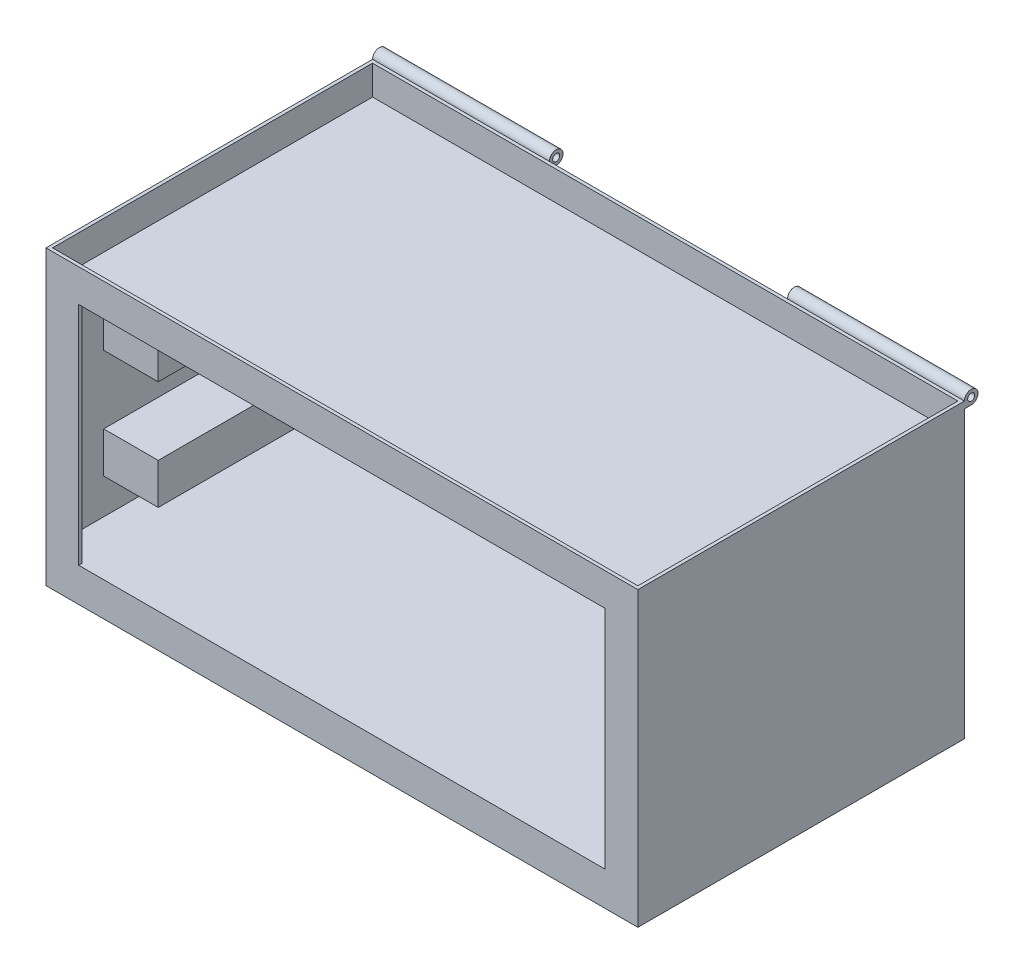
SolidWorks part; units mm, degrees
ref_plane "Front Plane" through (0, 0, 0) normal (0, 0, 1) x (1, 0, 0)
ref_plane "Top Plane" through (0, 0, 0) normal (0, 1, 0) x (1, 0, 0)
ref_plane "Right Plane" through (0, 0, 0) normal (1, 0, 0) x (0, 0, -1)
sketch "Sketch1" plane through (0, 0, 0) normal (0, 1, 0) x (1, 0, 0)
  line L0 (0, 0) -> (-1.524, 0) construction
  line L9 (0, 0) -> (273.177, 0)
  line L10 (0, 0) -> (0, 149.352)
  line L11 (0, 149.352) -> (273.177, 149.352)
  line L12 (273.177, 0) -> (273.177, 149.352)
  line L13 (-1.524, -1.524) -> (274.701, -1.524)
  line L14 (-1.524, -1.524) -> (-1.524, 150.876)
  line L15 (-1.524, 150.876) -> (274.701, 150.876)
  line L16 (274.701, -1.524) -> (274.701, 150.876)
  line L17 (0, 149.352) -> (0, 150.876) construction
  line L18 (273.177, 149.352) -> (274.701, 149.352) construction
  line L19 (273.177, 0) -> (273.177, -1.524) construction
  line L20 (13.716, 0) -> (13.716, -1.524)
  line L21 (136.5885, 150.876) -> (136.5885, -1.524) construction
  line L22 (259.461, 0) -> (259.461, -1.524)
  point P19 (0, 0)
  dimension "D1" = 1.524
  dimension "D2" = 276.225
  dimension "D3" = 152.4
  dimension "D4" = 15.24
extrude "Bulk-Extrude" add sketch "Sketch1" against normal blind 136.525 contours L14 L13 L16 L15
extrude "Inner Shell-Cut" cut sketch "Sketch1<13>" against normal offset from surface (120.65 mm away) 15.875 contours L9 L12 L11 L10 | L22 L9 L20 L13 region at (136.5885, 0, -74.676) region at (136.5885, 0, 0.762) up to face at (136.5885, -136.525, -74.676)
sketch "Sketch1<13>" plane through (0, 0, 0) normal (0, 1, 0) x (1, 0, 0) same geometry as "Sketch1"
extrude "Top Wall-Extrude" add sketch "Sketch1<14>" against normal blind 15.24 contours L22 L9 L20 L13 region at (136.5885, 0, 0.762)
sketch "Sketch1<14>" plane through (0, 0, 0) normal (0, 1, 0) x (1, 0, 0) same geometry as "Sketch1"
extrude "Top Floor-Extrude" add sketch "Sketch1<15>" along normal blind 1.524 from surface contours L9 L12 L11 L10 region at (136.5885, 0, -74.676) starting at face at (136.5885, -15.24, 0.762)
sketch "Sketch1<15>" plane through (0, 0, 0) normal (0, 1, 0) x (1, 0, 0) same geometry as "Sketch1"
ref_plane "Mid Plane" through (136.5885, 0, 0) normal (1, 0, 0) x (0, 0, -1)
sketch "Sketch5" plane through (274.701, 0, 0) normal (1, 0, 0) x (0, 0, -1)
  line L0 (150.876, 0) -> (154.051, 0)
  line L2 (154.051, -3.175) -> (150.876, -3.175)
  line L3 (150.876, -136.525) -> (150.876, 0) construction
  circle A0 centre (154.051, 0) radius 3.175
  circle A1 centre (154.051, 0) radius 1.651
  line M6 (150.876, -136.525) -> (150.876, 0)
  dimension "D1" = 1.524
  dimension "D2" = 6.35
extrude "Hinge-Extrude" add sketch "Sketch5" against normal blind 82.55 contours A1 A0 | A0 L2 M6 region at (274.701, 3.0852, -154.051) region at (274.701, -2.4658, -151.5852)
mirror "Mirror1" about plane through (136.5885, 0, 0) normal (1, 0, 0) of "Hinge-Extrude"
sketch "Sketch7" plane through (0, 0, -149.352) normal (0, 0, 1) x (1, 0, 0)
  line L0 (273.177, -120.65) -> (273.177, -15.24) construction
  line L1 (0, -34.29) -> (25.4635, -34.29)
  line L2 (0, -34.29) -> (0, -53.34)
  line L3 (0, -53.34) -> (25.4635, -53.34)
  line L4 (25.4635, -34.29) -> (25.4635, -53.34)
  line L5 (273.177, -34.29) -> (247.7135, -34.29)
  line L6 (273.177, -34.29) -> (273.177, -53.34)
  line L7 (273.177, -53.34) -> (247.7135, -53.34)
  line L8 (247.7135, -34.29) -> (247.7135, -53.34)
  line L9 (0, -120.65) -> (0, -15.24) construction
  line L10 (0, -85.09) -> (25.4635, -85.09)
  line L11 (0, -85.09) -> (0, -104.14)
  line L12 (0, -104.14) -> (25.4635, -104.14)
  line L13 (25.4635, -85.09) -> (25.4635, -104.14)
  line L14 (0, -15.24) -> (0, -34.29) construction
  line L15 (273.177, -85.09) -> (247.7135, -85.09)
  line L16 (273.177, -85.09) -> (273.177, -104.14)
  line L17 (273.177, -104.14) -> (247.7135, -104.14)
  line L18 (247.7135, -85.09) -> (247.7135, -104.14)
  line L19 (0, -15.24) -> (273.177, -15.24) construction
  line L20 (273.177, -15.24) -> (273.177, -34.29) construction
  line L21 (0, -53.34) -> (0, -85.09) construction
  line L22 (273.177, -53.34) -> (273.177, -85.09) construction
  dimension "D1" = 19.05
  dimension "D2" = 31.75
  dimension "D3" = 19.05
  dimension "D4" = 222.25
extrude "Rails-Extrude" add sketch "Sketch7" along normal offset from surface (125.476 mm away) 25.4 up to face at (136.5885, -68.2625, 1.524)
